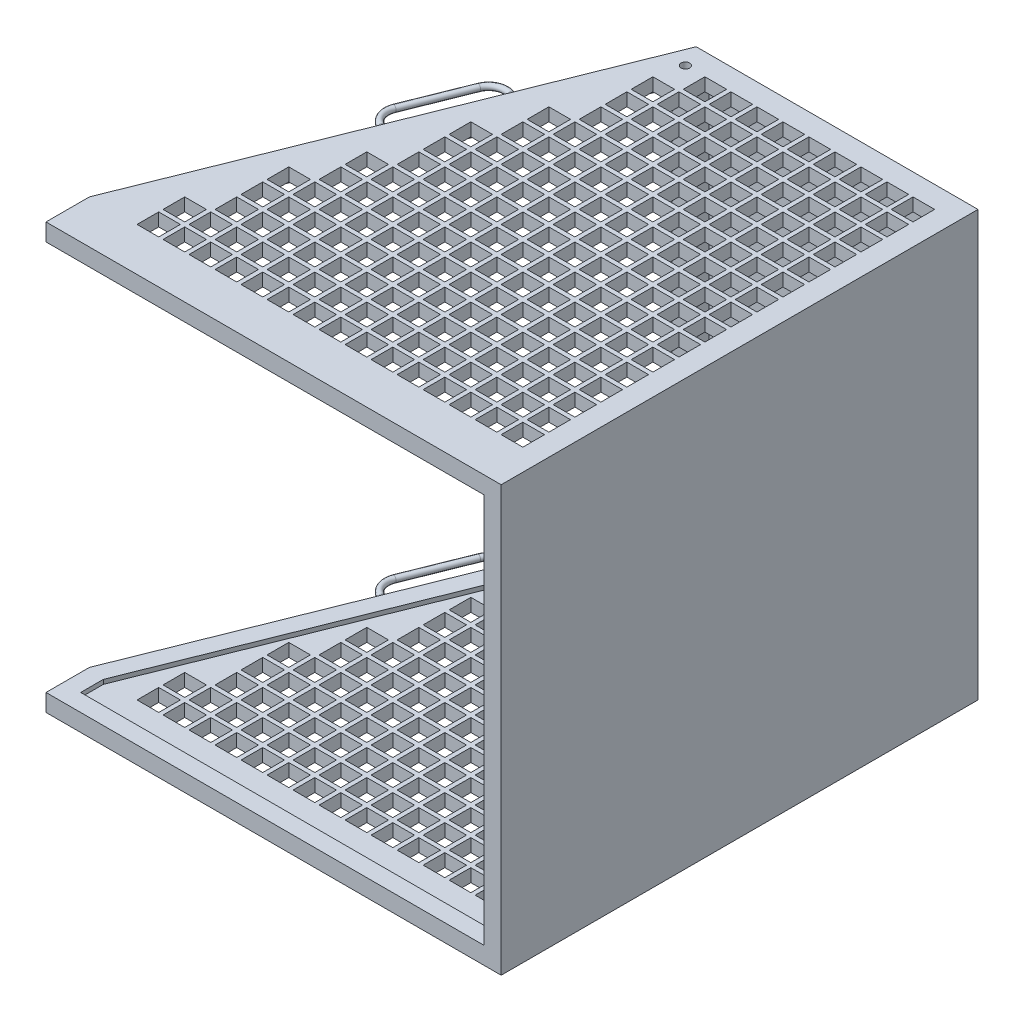
SolidWorks part; units mm, degrees
ref_plane "Front Plane" through (0, 0, 0) normal (0, 0, 1) x (1, 0, 0)
ref_plane "Top Plane" through (0, 0, 0) normal (0, 1, 0) x (1, 0, 0)
ref_plane "Right Plane" through (0, 0, 0) normal (1, 0, 0) x (0, 0, -1)
sketch "Sketch1" plane through (0, 0, 0) normal (0, 1, 0) x (1, 0, 0)
  line L0 (-533.1484, -550) -> (-533.1484, -450)
  line L1 (-133.1484, 550) -> (516.8516, 550)
  line L3 (-533.1484, -550) -> (516.8516, -550)
  line L4 (516.8516, 550) -> (516.8516, -550)
  line L5 (-533.1484, -450) -> (-133.1484, 550)
  point P0 (0, 0)
  dimension "D1" = 650
  dimension "D2" = 1100
  dimension "D3" = 1050
  dimension "D4" = 100
extrude "Boss-Extrude1" add sketch "Sketch1" along normal mid plane 980
sketch "Sketch2" plane through (0, 490, 0) normal (0, 1, 0) x (1, 0, 0)
  line L10 (476.8516, -510) -> (476.8516, 510)
  line L11 (476.8516, 510) -> (-106.0671, 510)
  line L12 (-106.0671, 510) -> (-493.1484, -457.7033)
  line L13 (-493.1484, -457.7033) -> (-493.1484, -510)
  line L14 (-493.1484, -510) -> (476.8516, -510)
  line L15 (476.8516, -510) -> (476.8516, 510)
  line L16 (476.8516, 510) -> (-106.0671, 510)
  line L17 (-106.0671, 510) -> (-493.1484, -457.7033)
  line L18 (-493.1484, -457.7033) -> (-493.1484, -510)
  line L19 (-493.1484, -510) -> (476.8516, -510)
  dimension "D1" = 40
extrude "Cut-Extrude1" cut sketch "Sketch2" against normal blind 980
sketch "Sketch3" plane through (0, 0, 0) normal (0, 1, 0) x (1, 0, 0)
  line L1 (476.8516, 510) -> (-533.1484, 510)
  line L2 (476.8516, 510) -> (476.8516, -550)
  line L3 (476.8516, -550) -> (-533.1484, -550)
  line L4 (-533.1484, 510) -> (-533.1484, -550)
extrude "Cut-Extrude2" cut sketch "Sketch3" against normal mid plane 900
sketch "Sketch5" plane through (0, 490, 0) normal (0, 1, 0) x (1, 0, 0)
  line L0 (-493.1484, -510) -> (-493.1484, -457.7033)
  line L1 (476.8516, 510) -> (-106.0671, 510)
  line L2 (476.8516, 510) -> (476.8516, -510)
  line L3 (476.8516, -510) -> (-493.1484, -510)
  line L5 (-493.1484, -457.7033) -> (-106.0671, 510)
extrude "Boss-Extrude2" add sketch "Sketch5" against normal blind 30
mirror "Mirror2" about plane through (0, 0, 0) normal (0, 1, 0) of "Boss-Extrude2"
sketch "Sketch6" plane through (0, 0, -510) normal (0, 0, 1) x (1, 0, 0)
  line L12 (-93.1484, -450) -> (476.8516, -450)
  line L13 (-93.1484, 450) -> (-93.1484, -450)
  line L14 (476.8516, 450) -> (-93.1484, 450)
  line L15 (476.8516, -450) -> (476.8516, 450)
  line L16 (-93.1484, -450) -> (476.8516, -450)
  line L17 (-93.1484, 450) -> (-93.1484, -450)
  line L18 (476.8516, 450) -> (-93.1484, 450)
  line L19 (476.8516, -450) -> (476.8516, 450)
  dimension "D1" = 40
extrude "Cut-Extrude3" cut sketch "Sketch6" against normal blind 50
sketch "Sketch7" plane through (476.8516, 0, 0) normal (-1, 0, 0) x (0, 0, 1)
  line L1 (-510, 450) -> (510, 450)
  line L2 (-510, 450) -> (-510, -450)
  line L3 (-510, -450) -> (510, -450)
  line L4 (510, 450) -> (510, -450)
extrude "Cut-Extrude5" cut sketch "Sketch7" against normal blind 30 contours L2 L3 L4 L1
sketch "Sketch9" plane through (0, 0, -550) normal (0, 0, -1) x (-1, 0, 0)
  line L14 (103.1484, -460) -> (103.1484, 460)
  line L15 (-486.8516, -460) -> (103.1484, -460)
  line L16 (-486.8516, 460) -> (-486.8516, -460)
  line L17 (103.1484, 460) -> (-486.8516, 460)
  line L18 (103.1484, -460) -> (103.1484, 460)
  line L19 (-486.8516, -460) -> (103.1484, -460)
  line L20 (-486.8516, 460) -> (-486.8516, -460)
  line L21 (103.1484, 460) -> (-486.8516, 460)
  dimension "D1" = 10
extrude "Cut-Extrude6" cut sketch "Sketch9" against normal blind 10
sketch "Sketch10" plane through (0, 490, 0) normal (0, 1, 0) x (1, 0, 0)
  line L5 (466.8516, 500) -> (416.8516, 500)
  line L6 (466.8516, 500) -> (466.8516, 450)
  line L7 (466.8516, 450) -> (416.8516, 450)
  line L8 (416.8516, 500) -> (416.8516, 450)
  dimension "D1" = 50
extrude "Cut-Extrude8" cut sketch "Sketch10" against normal through all contours L7 L8 L5 L6
pattern_linear "LPattern1" count 15 spacing 60 along (-1, 0, 0) count 16 spacing 60 along (0, 0, 1) skipping (9, 0), (10, 0), (10, 1), (10, 2), (10, 3), (11, 0), (11, 1), (11, 2), (11, 3), (11, 4), (11, 5), (12, 0), (12, 1), (12, 2), (12, 3), (12, 4), (12, 5), (12, 6), (12, 7), (12, 8), (13, 0), (13, 1), (13, 2), (13, 3), (13, 4), (13, 5), (13, 6), (13, 7), (13, 8), (13, 9), (13, 10), (14, 0), (14, 1), (14, 2), (14, 3), (14, 4), (14, 5), (14, 6), (14, 7), (14, 8), (14, 9), (14, 10), (14, 11), (14, 12), (14, 13) of "Cut-Extrude8"
sketch "Sketch11" plane through (0, 490, 0) normal (0, 1, 0) x (1, 0, 0)
  circle A0 centre (-108.1484, 500) radius 10
  dimension "D1" = 20
  dimension "D2" = 25
  dimension "D3" = 50
extrude "Cut-Extrude9" cut sketch "Sketch11" against normal through all
sketch "Sketch12" plane through (0, 0, -540) normal (0, 0, -1) x (-1, 0, 0)
  line L1 (-486.8516, 460) -> (103.1484, 460)
  line L2 (-486.8516, 460) -> (-486.8516, -460)
  line L3 (-486.8516, -460) -> (103.1484, -460)
  line L4 (103.1484, 460) -> (103.1484, -460)
extrude "Boss-Extrude3" add sketch "Sketch12" along normal blind 5 separate body
ref_plane "Plane2" through (0, 470, 0) normal (0, 1, 0) x (1, 0, 0)
sketch "Sketch13" plane through (0, 470, 0) normal (0, 1, 0) x (1, 0, 0)
  line L0 (-251.9934, 252.8875) -> (-270.563, 260.3153)
  line L1 (-133.1484, 550) -> (-533.1484, -450) construction
  line L2 (-322.5576, 238.0318) -> (-378.2663, 98.7603)
  line L3 (-355.9828, 46.7656) -> (-337.4133, 39.3378)
  arc A0 (-378.2663, 98.7603) -> (-355.9828, 46.7656) centre (-341.1272, 83.9047) ccw
  arc A1 (-270.563, 260.3153) -> (-322.5576, 238.0318) centre (-285.4186, 223.1762) ccw
  point P9 (-393.1219, 61.6213)
  point P12 (-307.702, 275.1709)
  dimension "D4" = 40
  dimension "D1" = 60
  dimension "D2" = 230
  dimension "D3" = 320
sketch "Sketch14" plane through (-304.4383, 0, -121.7753) normal (-0.9285, 0, -0.3714) x (-0.3714, 0, 0.9285)
  circle A0 centre (-141.2121, 470) radius 7
  dimension "D1" = 14
sweep "Sweep1" add profiles "Sketch14" path "Sketch13"
mirror "Mirror3" about plane through (0, 0, 0) normal (0, 1, 0) of "Sweep1"
